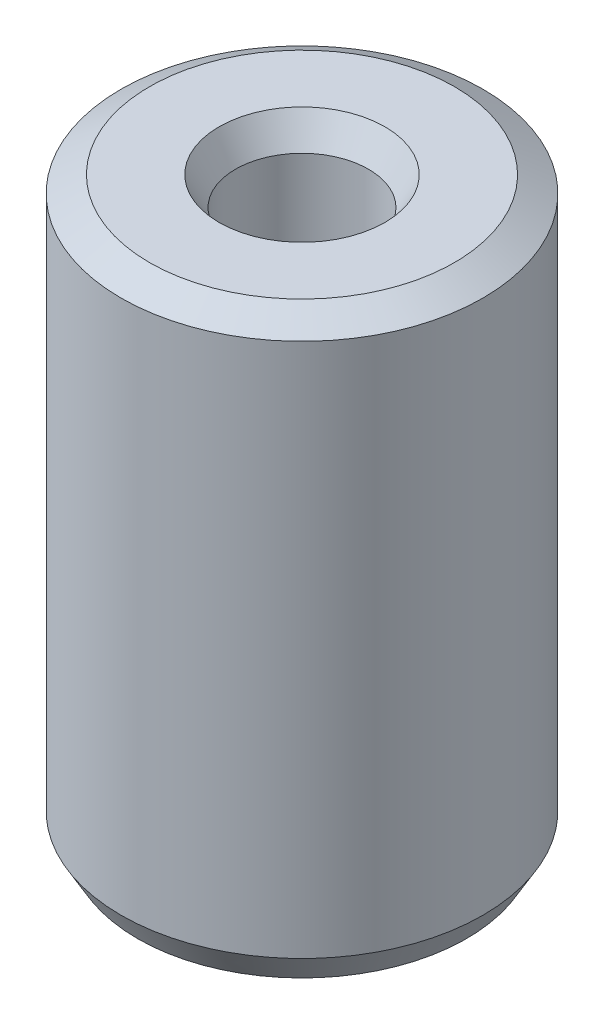
SolidWorks part; units mm, degrees
ref_plane "Front Plane" through (0, 0, 0) normal (0, 0, 1) x (1, 0, 0)
ref_plane "Top Plane" through (0, 0, 0) normal (0, 1, 0) x (1, 0, 0)
ref_plane "Right Plane" through (0, 0, 0) normal (1, 0, 0) x (0, 0, -1)
sketch "Sketch1" plane through (0, 0, 0) normal (0, 1, 0) x (1, 0, 0)
  circle A0 centre (0, 0) radius 20
  dimension "SLEEVE_OD" = 40
extrude "Boss-Extrude1" add sketch "Sketch1" along normal blind 64.0483
sketch "Sketch2" plane through (0, 0, 0) normal (0, 1, 0) x (1, 0, 0)
  circle A0 centre (0, 0) radius 7.3478
  dimension "BORE_D" = 14.6957
extrude "Cut-Extrude1" cut sketch "Sketch2" along normal through all
chamfer "Chamfer1" distance 1.8186 angle 60 4 edges at (0, 64.0483, 7.3478) (0, 0, 7.3478) (0, 0, 20) (0, 64.0483, 20) first distance on face at (0, 64.0483, 7.3478) first distance on face at (0, 0, 7.3478) first distance on face at (0, 64.0483, 20)
